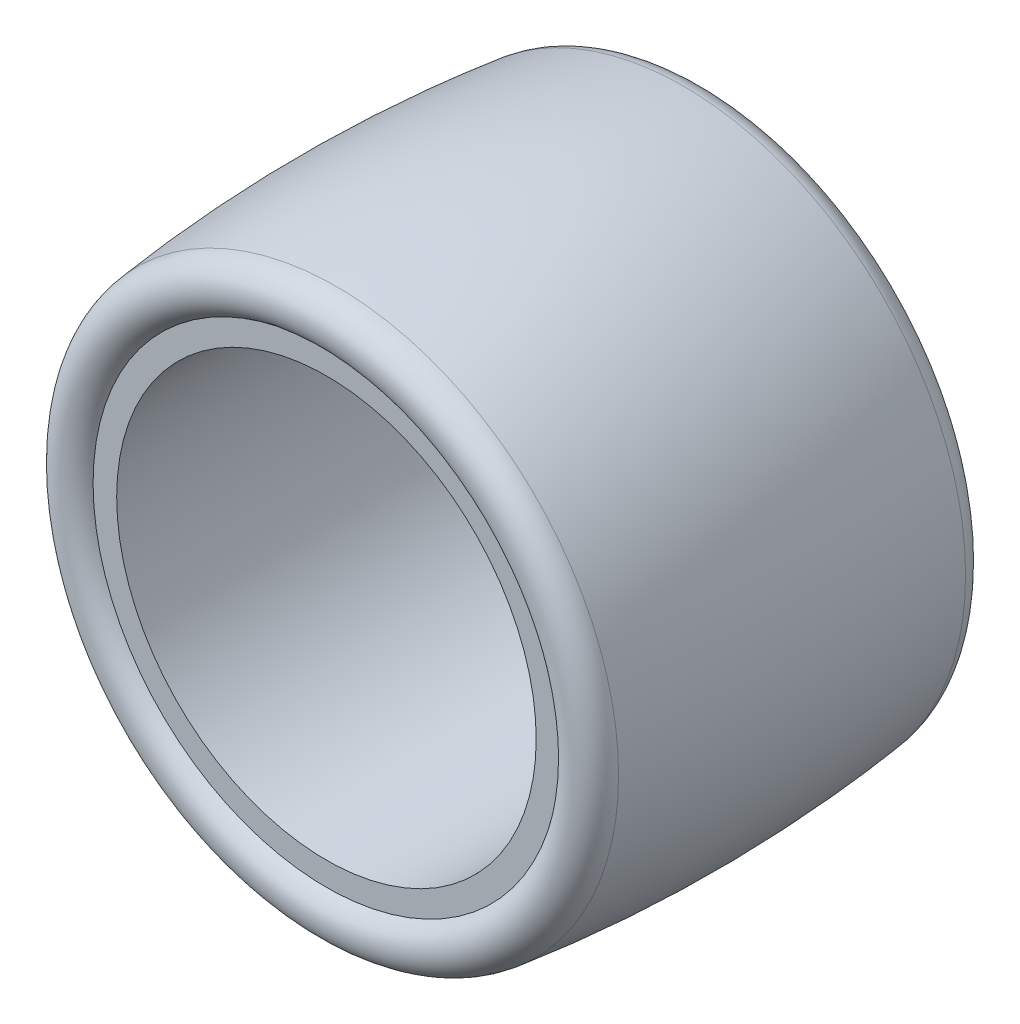
SolidWorks part; units mm, degrees
ref_plane "Front Plane" through (0, 0, 0) normal (0, 0, 1) x (1, 0, 0)
ref_plane "Top Plane" through (0, 0, 0) normal (0, 1, 0) x (1, 0, 0)
ref_plane "Right Plane" through (0, 0, 0) normal (1, 0, 0) x (0, 0, -1)
sketch "Sketch1" plane through (0, 0, 0) normal (0, 0, 1) x (1, 0, 0)
  circle A0 centre (0, 0) radius 40
  circle A1 centre (0, 0) radius 44.5
  dimension "D1" = 80
  dimension "D2" = 4.5
extrude "Boss-Extrude1" add sketch "Sketch1" along normal mid plane 70
sketch "Sketch3" plane through (0, 0, 0) normal (1, 0, 0) x (0, 0, -1)
  line L0 (-49.8156, 0) -> (52.507, 0) construction
  line L1 (0, 0) -> (0, 55.75) construction
  line L2 (-37.5, 0) -> (-37.5, 66.5822) construction
  line L3 (-35, 44.5) -> (-35, -44.5) construction
  line L4 (-35, 44.5) -> (-35, -44.5) construction
  line L5 (-29.9969, 55.75) -> (30.4614, 55.75) construction
  line L6 (-35, 44.5) -> (35, 44.5)
  arc A0 (-33.0887, 53.7954) -> (-35, 44.5) centre (-32.5, 48.8301) ccw
  arc A1 (35, 44.5) -> (33.0887, 53.7954) centre (32.5, 48.8301) ccw
  arc A2 (-33.0887, 53.7954) -> (33.0887, 53.7954) centre (0, -225.2932) cw
  point P18 (-36.9338, 46.519)
  dimension "D1" = 10
  dimension "D2" = 2.5
  dimension "D3" = 55.75
revolve "Revolve1" add sketch "Sketch3" angle 360 about L0
